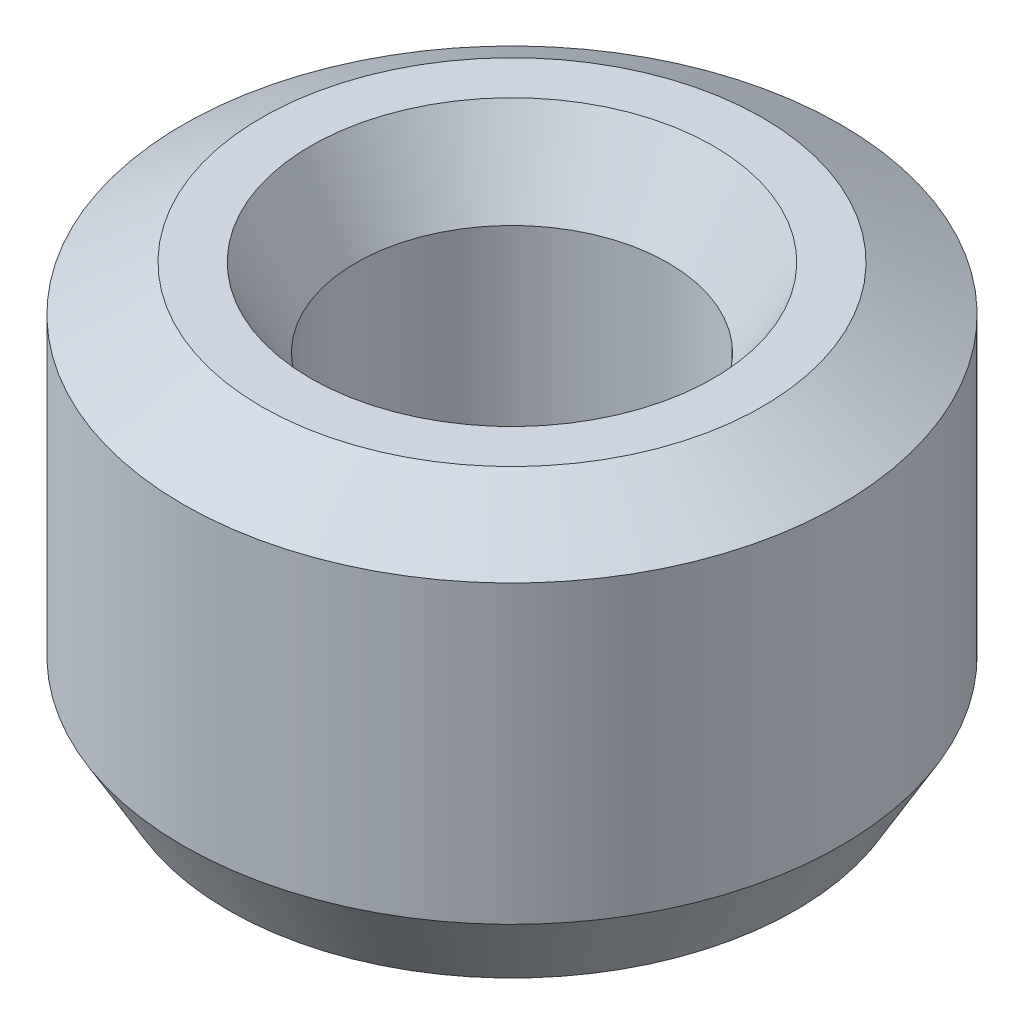
SolidWorks part; units mm, degrees
ref_plane "Front Plane" through (0, 0, 0) normal (0, 0, 1) x (1, 0, 0)
ref_plane "Top Plane" through (0, 0, 0) normal (0, 1, 0) x (1, 0, 0)
ref_plane "Right Plane" through (0, 0, 0) normal (1, 0, 0) x (0, 0, -1)
sketch "Sketch1" plane through (0, 0, 0) normal (0, 1, 0) x (1, 0, 0)
  circle A0 centre (0, 0) radius 10
  dimension "SLEEVE_OD" = 20
extrude "Boss-Extrude1" add sketch "Sketch1" along normal blind 12.755
sketch "Sketch2" plane through (0, 0, 0) normal (0, 1, 0) x (1, 0, 0)
  circle A0 centre (0, 0) radius 4.7437
  dimension "BORE_D" = 9.4875
extrude "Cut-Extrude1" cut sketch "Sketch2" along normal through all
chamfer "Chamfer1" distance 1.3788 angle 60 4 edges at (0, 12.755, 4.7437) (0, 0, 4.7437) (0, 0, 10) (0, 12.755, 10) first distance on face at (0, 12.755, 4.7437) first distance on face at (0, 0, 4.7437) first distance on face at (0, 12.755, 10)
